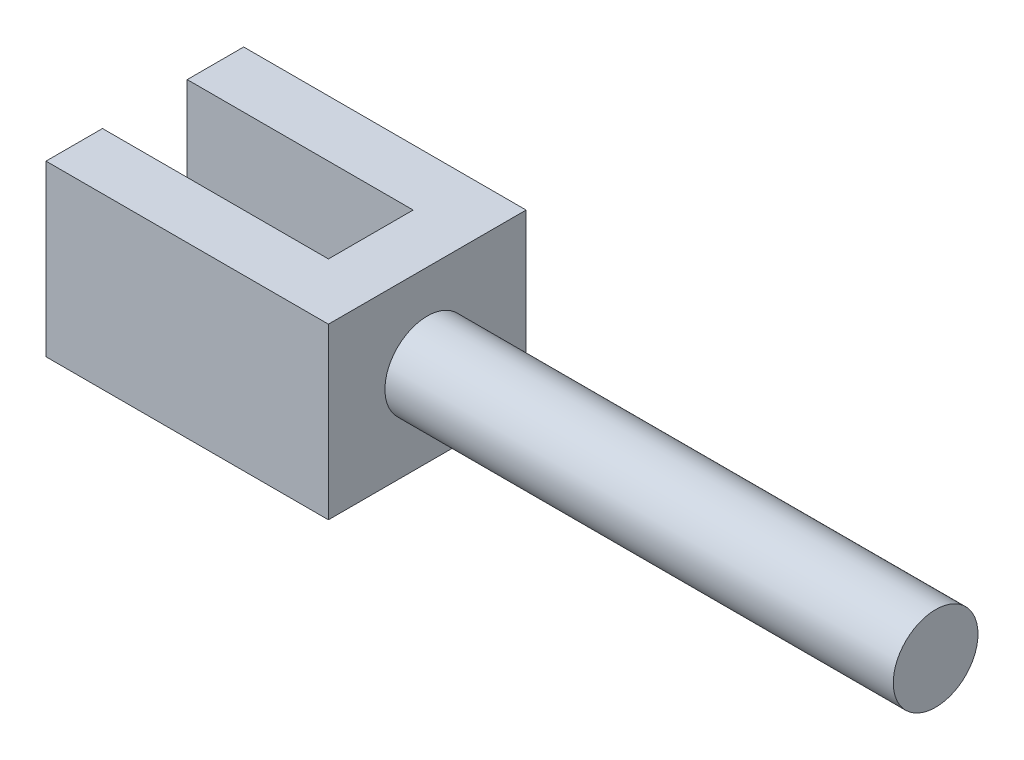
SolidWorks part; units mm, degrees
ref_plane "Front Plane" through (0, 0, 0) normal (0, 0, 1) x (1, 0, 0)
ref_plane "Top Plane" through (0, 0, 0) normal (0, 1, 0) x (1, 0, 0)
ref_plane "Right Plane" through (0, 0, 0) normal (1, 0, 0) x (0, 0, -1)
sketch "Sketch1" plane through (0, 0, 0) normal (1, 0, 0) x (0, 0, -1)
  circle A0 centre (0, 0) radius 0.75
  dimension "D1" = 1.5
extrude "Boss-Extrude1" add sketch "Sketch1" along normal blind 10
sketch "Sketch2" plane through (0, 0, 0) normal (0, 1, 0) x (1, 0, 0)
  line L0 (1, 1.75) -> (1, -1.75)
  line L2 (0, 0.75) -> (0, -0.75)
  line L5 (1, -1.75) -> (-4, -1.75)
  line L6 (-4, 1.75) -> (-4, 0.75)
  line L7 (1, 1.75) -> (-4, 1.75)
  line L8 (0, 0.75) -> (-4, 0.75)
  line L10 (-4, -0.75) -> (0, -0.75)
  line L11 (-4, -0.75) -> (-4, -1.75)
  line L13 (-4, 1.75) -> (-4, -1.75) construction
  line L14 (-3, 0.75) -> (-3, -0.75) construction
  line L15 (0, 0.75) -> (-3, 0.75) construction
  line L16 (0, -0.75) -> (-3, -0.75) construction
  dimension "D2" = 1
extrude "Boss-Extrude2" add sketch "Sketch2" along normal blind 1.5 and the other way blind 1.5
